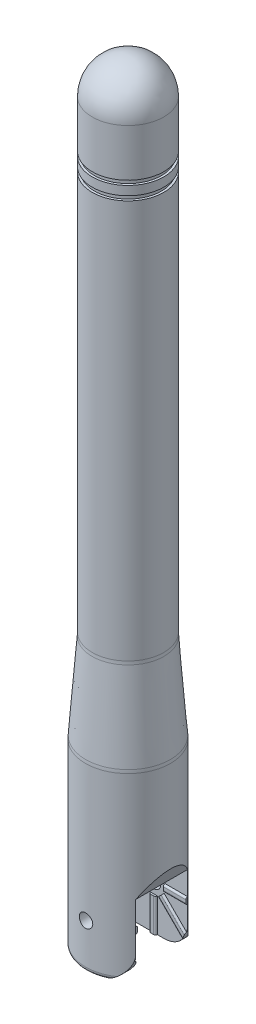
SolidWorks part; units mm, degrees
ref_plane "Plan de face" through (0, 0, 0) normal (0, 0, 1) x (1, 0, 0)
ref_plane "Plan de dessus" through (0, 0, 0) normal (0, 1, 0) x (1, 0, 0)
ref_plane "Plan de droite" through (0, 0, 0) normal (1, 0, 0) x (0, 0, -1)
sketch "Esquisse2" plane through (0, 0, 0) normal (0, 0, 1) x (1, 0, 0)
  line L0 (0, 0) -> (0, 86.4522) construction
  line L1 (0, 86.4522) -> (4, 86.4522) construction
  line L2 (4, 86.4522) -> (4, 0) construction
  line L3 (4, 0) -> (0, 0) construction
  line L4 (4, 0) -> (4.75, 0) construction
  line L5 (4.75, 0) -> (4.75, 20.4) construction
  line L6 (4.75, 20.4) -> (0, 20.4) construction
  line L7 (4, 82.4522) -> (4, 30.5872) construction
  line L8 (4.014, 30.2133) -> (4.736, 20.5867)
  line L9 (4.75, 20.2128) -> (4.75, 0)
  line L10 (4.75, 0) -> (1, 0)
  line L11 (1, 0) -> (1, 82.4522)
  line L12 (1, 82.4522) -> (0, 82.4522)
  line L13 (4, 82.4522) -> (4, 77.1522)
  line L14 (4, 77.1522) -> (3.75, 77.1522)
  line L15 (3.75, 77.1522) -> (3.75, 76.6522)
  line L16 (3.75, 76.6522) -> (4, 76.6522)
  line L17 (4, 76.6522) -> (4, 75.6522)
  line L18 (4, 75.6522) -> (3.75, 75.6522)
  line L19 (3.75, 75.6522) -> (3.75, 75.1522)
  line L20 (3.75, 75.1522) -> (4, 75.1522)
  line L21 (0, 86.4522) -> (0, 82.4522)
  line L22 (4, 75.1522) -> (4, 30.5872)
  arc A0 (0, 86.4522) -> (4, 82.4522) centre (0, 82.4522) cw
  arc A1 (4.75, 20.2128) -> (4.736, 20.5867) centre (-0.25, 20.2128) ccw
  arc A2 (4.014, 30.2133) -> (4, 30.5872) centre (9, 30.5872) cw
  point P18 (4, 30.4)
  point P25 (3.875, 75.6522)
  dimension "D7" = 5
  dimension "D1" = 86.4522
  dimension "D2" = 8
  dimension "D3" = 9.5
  dimension "D4" = 20.4
  dimension "D5" = 2
  dimension "D6" = 10
  dimension "D8" = 9.3
  dimension "D9" = 0.5
  dimension "D10" = 1.5
  dimension "D11" = 7.5
revolve "Révolution1" add sketch "Esquisse2" angle 360 about L0
sketch "Esquisse3" plane through (0, 0, 0) normal (0, -1, 0) x (1, 0, 0)
  line L0 (0, 0) -> (-2.75, 0) construction
  line L1 (-2.75, 2.9) -> (4.75, 2.9)
  line L2 (-2.75, 2.9) -> (-2.75, -2.9)
  line L3 (-2.75, -2.9) -> (4.75, -2.9)
  line L4 (4.75, 2.9) -> (4.75, -2.9)
  line L5 (-4.75, 0) -> (-2.75, 0) construction
  circle A0 centre (0, 0) radius 4.75 construction
  dimension "D1" = 5.8
  dimension "D2" = 2
extrude "Enlèv. mat.-Extru.1" cut sketch "Esquisse3" against normal blind 8
fillet "Congé1" radius 0.5 1 edges at (-4.75, 0, 0)
sketch "Esquisse4" plane through (0, 0, 0) normal (0, 0, 1) x (1, 0, 0)
  line L0 (3.762, 8) -> (3.762, 0.5) construction
  line L1 (-4.75, 0) -> (3.762, 0) construction
  line L2 (1.162, 0) -> (3.762, 0)
  line L3 (3.762, 0) -> (3.762, 2.6)
  line L4 (0, 0) -> (0, 5) construction
  line L5 (3.762, 8) -> (4.75, 10)
  line L6 (4.75, 8) -> (4.75, 20.2128) construction
  line L7 (4.75, 10) -> (4.75, 8)
  line L8 (3.762, 8) -> (4.75, 8) construction
  line L9 (4.75, 8) -> (3.762, 8)
  arc A0 (3.762, 2.6) -> (1.162, 0) centre (1.162, 2.6) cw
  circle A1 centre (0, 5) radius 0.75
  dimension "D1" = 2.6
  dimension "D3" = 1.5
  dimension "D2" = 5
  dimension "D4" = 2
extrude "Enlèv. mat.-Extru.2" cut sketch "Esquisse4" against normal through all both and the other way through all
sketch "Esquisse5" plane through (0, 0, -2.9) normal (0, 0, 1) x (1, 0, 0)
  line L0 (-4.25, 0) -> (1.162, 0) construction
  line L1 (-0.375, 0) -> (0.375, 0)
  line L2 (-0.375, 0) -> (-0.375, 3.75)
  line L3 (-0.375, 3.75) -> (0.375, 3.75)
  line L4 (0.375, 0) -> (0.375, 3.75)
  line L5 (0, 5) -> (0, 3.75) construction
  line L6 (0, 5) -> (3.762, 1.238) construction
  line L7 (3.762, 8) -> (3.762, 2.6) construction
  line L8 (0.6187, 3.851) -> (3.4968, 0.9729) construction
  line L9 (0.6187, 3.851) -> (1.149, 4.3813)
  line L10 (3.4968, 0.9729) -> (4.0271, 1.5032)
  line L11 (1.149, 4.3813) -> (4.0271, 1.5032) construction
  line L12 (0.6187, 3.851) -> (4.0271, 1.5032) construction
  line L13 (3.4968, 0.9729) -> (1.149, 4.3813) construction
  line L14 (1.149, 4.3813) -> (4.0271, 1.5032)
  line L15 (0.6187, 3.851) -> (3.4968, 0.9729)
  line L16 (0, 5) -> (3.762, 5) construction
  line L18 (1.25, 4.625) -> (3.762, 4.625)
  line L19 (1.25, 4.625) -> (1.25, 5.375)
  line L20 (1.25, 5.375) -> (3.762, 5.375)
  line L21 (3.762, 4.625) -> (3.762, 5.375)
  line L22 (1.25, 4.625) -> (3.762, 5.375) construction
  line L23 (1.25, 5.375) -> (3.762, 4.625) construction
  point P13 (2.3229, 2.6771)
  point P18 (2.506, 5)
  dimension "D1" = 0.75
  dimension "D2" = 1.25
  dimension "D3" = 45
  dimension "D4" = 1.25
  dimension "D5" = 1.25
extrude "Boss.-Extru.1" add sketch "Esquisse5" along normal blind 0.2
fillet "Congé2" radius 0.2 6 edges at (2.506, 5.375, -2.7) (2.506, 4.625, -2.7) (2.5881, 2.9422, -2.7) (2.0578, 2.4119, -2.7) (-0.375, 1.875, -2.7) (0.375, 1.875, -2.7)
mirror "Symétrie1" about plane through (0, 0, 0) normal (0, 0, 1) of "Congé2", "Boss.-Extru.1"
sketch "Esquisse6" plane through (0, 0, 2.9) normal (0, 0, 1) x (1, 0, 0)
  line L3 (4.0271, 1.5032) -> (3.6581, 1.8723)
  line L4 (3.3199, 1.1497) -> (3.4968, 0.9729)
  line L5 (3.4968, 0.9729) -> (4.0271, 1.5032)
  line L6 (4.0271, 1.5032) -> (3.6581, 1.8723)
  line L7 (3.3199, 1.1497) -> (3.4968, 0.9729)
  line L8 (3.4968, 0.9729) -> (4.0271, 1.5032)
  arc A1 (3.3199, 1.1497) -> (3.6581, 1.8723) centre (1.162, 2.6) ccw
  arc A2 (3.3199, 1.1497) -> (3.6581, 1.8723) centre (1.162, 2.6) ccw
  dimension "D1" = 0
extrude "Enlèv. mat.-Extru.3" cut sketch "Esquisse6" against normal through all
